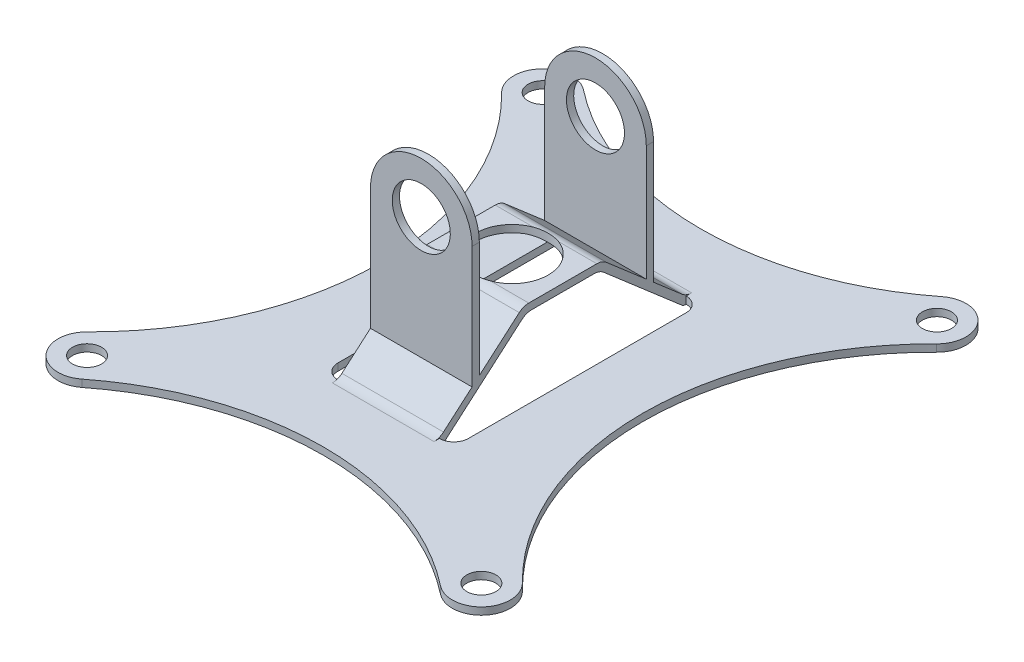
SolidWorks part; units mm, degrees
ref_plane "Front Plane" through (0, 0, 0) normal (0, 0, 1) x (1, 0, 0)
ref_plane "Top Plane" through (0, 0, 0) normal (0, 1, 0) x (1, 0, 0)
ref_plane "Right Plane" through (0, 0, 0) normal (1, 0, 0) x (0, 0, -1)
sketch "Sketch1" plane through (0, 0, 0) normal (0, 1, 0) x (1, 0, 0)
  line L0 (-86.233, 99.6442) -> (86.233, 99.6442) construction
  line L1 (-12.7, 0) -> (12.7, 0) construction
  line L2 (-86.233, -99.6442) -> (86.233, -99.6442) construction
  line L3 (0, -53.975) -> (0, 53.975) construction
  line L4 (-22.225, -53.975) -> (22.225, -53.975)
  line L5 (-28.575, -47.625) -> (-28.575, 47.625)
  line L6 (-22.225, 53.975) -> (22.225, 53.975)
  line L7 (28.575, -47.625) -> (28.575, 47.625)
  line L8 (-28.575, -53.975) -> (28.575, 53.975) construction
  line L9 (-28.575, 53.975) -> (28.575, -53.975) construction
  circle A0 centre (-86.233, 99.6442) radius 6.35
  circle A1 centre (86.233, 99.6442) radius 6.35
  arc A2 (-78.3936, 109.6359) -> (-95.1343, 90.5856) centre (-86.233, 99.6442) ccw
  arc A3 (95.1343, 90.5856) -> (78.3936, 109.6359) centre (86.233, 99.6442) ccw
  arc A4 (-78.3936, 109.6359) -> (78.3936, 109.6359) centre (0, 209.5531) ccw
  arc A5 (-78.3936, -109.6359) -> (78.3936, -109.6359) centre (0, -209.5531) cw
  arc A6 (95.1343, -90.5856) -> (78.3936, -109.6359) centre (86.233, -99.6442) cw
  arc A7 (-78.3936, -109.6359) -> (-95.1343, -90.5856) centre (-86.233, -99.6442) cw
  circle A8 centre (86.233, -99.6442) radius 6.35
  circle A9 centre (-86.233, -99.6442) radius 6.35
  arc A10 (-95.1343, 90.5856) -> (-95.1343, -90.5856) centre (-184.1469, 0) cw
  arc A11 (95.1343, 90.5856) -> (95.1343, -90.5856) centre (184.1469, 0) ccw
  arc A12 (-22.225, 53.975) -> (-28.575, 47.625) centre (-22.225, 47.625) ccw
  arc A13 (22.225, 53.975) -> (28.575, 47.625) centre (22.225, 47.625) cw
  arc A14 (22.225, -53.975) -> (28.575, -47.625) centre (22.225, -47.625) ccw
  arc A15 (-28.575, -47.625) -> (-22.225, -53.975) centre (-22.225, -47.625) ccw
  arc A21 (90.6836, 95.1149) -> (82.3133, 104.6401) centre (86.233, 99.6442) ccw
  arc A23 (-82.3133, 104.6401) -> (-90.6836, 95.1149) centre (-86.233, 99.6442) ccw
  arc A25 (-82.3133, -104.6401) -> (-90.6836, -95.1149) centre (-86.233, -99.6442) cw
  arc A27 (90.6836, -95.1149) -> (82.3133, -104.6401) centre (86.233, -99.6442) cw
  arc A29 (-82.3133, -104.6401) -> (82.3133, -104.6401) centre (0, -209.5531) cw construction
  arc A30 (-82.3133, 104.6401) -> (82.3133, 104.6401) centre (0, 209.5531) ccw construction
  arc A34 (-90.6836, 95.1149) -> (-90.6836, -95.1149) centre (-184.1469, 0) cw construction
  arc A35 (90.6836, 95.1149) -> (90.6836, -95.1149) centre (184.1469, 0) ccw construction
  point P4 (0, 99.6442)
  point P13 (0, 0)
  point P26 (0, 0)
  dimension "D1" = 172.466
  dimension "D3" = 12.7
  dimension "D4" = 127
  dimension "D6" = 127
  dimension "D7" = 25.4
  dimension "D11" = 6.35
  dimension "D2" = 99.6442
  dimension "D5" = 25.4
  dimension "D9" = 57.15
  dimension "D10" = 107.95
  dimension "D14" = 6.35
extrude "Boss-Extrude1" add sketch "Sketch1" along normal blind 3.175
sketch "Sketch4" plane through (0, 0, 0) normal (1, 0, 0) x (0, 0, -1)
  line L0 (-90.5856, 0) -> (90.5856, 0) construction
  line L1 (-53.975, 3.175) -> (-19.05, 33.3781)
  line L2 (-14.8963, 34.925) -> (14.8963, 34.925)
  line L3 (-36.5125, 18.2765) -> (-36.5125, 3.175) construction
  line L4 (90.5856, 3.175) -> (-90.5856, 3.175) construction
  line L5 (-51.8982, 0.7735) -> (-17.8676, 30.2031)
  line L6 (-13.7139, 31.75) -> (13.7139, 31.75)
  line L7 (-53.975, 3.175) -> (-53.975, 0)
  line L8 (0, 34.925) -> (0, 0) construction
  line L9 (36.5125, 18.2765) -> (36.5125, 3.175) construction
  line L10 (53.975, 3.175) -> (53.975, 0)
  line L11 (51.8982, 0.7735) -> (17.8676, 30.2031)
  line L12 (53.975, 3.175) -> (19.05, 33.3781)
  line L13 (-36.5125, 18.2765) -> (-36.5125, 91.0082)
  line L14 (-36.5125, 91.0082) -> (-39.6875, 91.0082)
  line L15 (-39.6875, 91.0082) -> (-39.6875, 15.5308)
  line L16 (39.6875, 91.0082) -> (39.6875, 15.5308)
  line L17 (36.5125, 91.0082) -> (39.6875, 91.0082)
  line L18 (36.5125, 18.2765) -> (36.5125, 91.0082)
  arc A0 (-53.975, 0) -> (-51.8982, 0.7735) centre (-53.975, 3.175) ccw
  arc A1 (-17.8676, 30.2031) -> (-13.7139, 31.75) centre (-13.7139, 25.4) cw
  arc A2 (-19.05, 33.3781) -> (-14.8963, 34.925) centre (-14.8963, 28.575) cw
  arc A3 (19.05, 33.3781) -> (14.8963, 34.925) centre (14.8963, 28.575) ccw
  arc A4 (17.8676, 30.2031) -> (13.7139, 31.75) centre (13.7139, 25.4) ccw
  arc A5 (53.975, 0) -> (51.8982, 0.7735) centre (53.975, 3.175) cw
  point P33 (0, 31.75)
  dimension "D1" = 31.75
  dimension "D5" = 6.35
  dimension "D2" = 3.175
  dimension "D3" = 3.175
  dimension "D4" = 36.5125
  dimension "D6" = 87.8332
extrude "Boss-Extrude3" add sketch "Sketch4" along normal mid plane 44.45 contours A5 L10 L12 A3 L2 A2 L1 L7 A0 L5 A1 L6 A4 L11 | L14 L15 L1 L13 | L18 L12 L16 L17 region at (0, 8.4947, 46.0891) region at (0, 53.9517, 38.1098) region at (0, 53.9517, -38.1098)
sketch "Sketch5" plane through (0, 34.925, 0) normal (0, 1, 0) x (1, 0, 0)
  circle A0 centre (0, 0) radius 15.875
  dimension "D1" = 31.75
extrude "Cut-Extrude1" cut sketch "Sketch5" against normal through all
sketch "Sketch6" plane through (0, 0, -39.6875) normal (0, 0, -1) x (-1, 0, 0)
  line L0 (-22.225, 91.0082) -> (22.225, 91.0082) construction
  line L1 (22.225, 91.0082) -> (22.225, 15.5308) construction
  line L2 (-22.225, 91.0082) -> (-22.225, 15.5308) construction
  line L3 (22.225, 91.0082) -> (22.225, 15.5308)
  line L4 (-22.225, 91.0082) -> (-22.225, 15.5308)
  line L5 (-22.225, 91.0082) -> (22.225, 91.0082)
  circle A0 centre (0, 68.7832) radius 22.225
  circle A1 centre (0, 68.7832) radius 12.7
  line M4 (22.225, 91.0082) -> (-22.225, 91.0082)
  line M5 (-22.225, 91.0082) -> (-22.225, 15.5308)
  dimension "D1" = 44.45
  dimension "D2" = 25.4
extrude "Cut-Extrude2" cut sketch "Sketch6" against normal up to surface (79.375 mm away) contours A1 | A0 L5 M5 | A0 L3 M4 region at (-17.2606, 86.0438, -39.6875) region at (17.2606, 86.0438, -39.6875) region at (0, 68.7832, -39.6875) up to face at (0, 53.2695, 39.6875)
fillet "Fillet1" radius 6.35 2 edges at (0, 3.175, 53.975) (0, 3.175, -53.975)
extrude "holes" cut sketch "Sketch1<5>" along normal through all contours A9 | A8 | A0 | A1 region at (-86.233, 0, -99.6442) region at (86.233, 0, -99.6442) region at (86.233, 0, 99.6442) region at (-86.233, 0, 99.6442)
sketch "Sketch1<5>" plane through (0, 0, 0) normal (0, 1, 0) x (1, 0, 0) same geometry as "Sketch1"
sketch "Sketch7" plane through (0, 3.175, 0) normal (0, 1, 0) x (1, 0, 0)
  line L0 (-86.233, 99.6442) -> (86.233, -99.6442) construction
  line L1 (-86.233, -99.6442) -> (86.233, 99.6442) construction
  line L2 (0, 82.5531) -> (0, -82.5531) construction
  circle A0 centre (-73.7669, 85.2394) radius 6.35
  circle A1 centre (-73.7669, -85.2394) radius 6.35
  circle A2 centre (-86.233, -99.6442) radius 6.35 construction
  arc A3 (-78.3936, 109.6359) -> (78.3936, 109.6359) centre (0, 209.5531) ccw construction
  arc A4 (78.3936, -109.6359) -> (-78.3936, -109.6359) centre (0, -209.5531) ccw construction
  circle A5 centre (73.7669, -85.2394) radius 6.35
  circle A6 centre (73.7669, 85.2394) radius 6.35
  circle A10 centre (-86.233, 99.6442) radius 6.35 construction
  circle A11 centre (86.233, -99.6442) radius 6.35 construction
  dimension "D1" = 19.05
  dimension "D2" = 19.05
extrude "DH" [suppressed] cut sketch "Sketch7" against normal through all
sketch "Sketch8" plane through (0, 3.175, 0) normal (0, 1, 0) x (1, 0, 0)
  line L0 (0, 82.5531) -> (0, -82.5531) construction
  arc A0 (-81.7824, 104.1735) -> (-81.7824, -104.1735) centre (-184.1469, 0) cw
  circle A1 centre (-86.233, -99.6442) radius 6.35 construction
  circle A2 centre (-86.233, 99.6442) radius 6.35 construction
  arc A3 (-95.1343, -90.5856) -> (-95.1343, 90.5856) centre (-184.1469, 0) ccw construction
  arc A4 (-90.6836, 95.1149) -> (-90.6836, -95.1149) centre (-184.1469, 0) cw
  arc A5 (-90.6836, -95.1149) -> (-81.7824, -104.1735) centre (-86.233, -99.6442) ccw
  arc A6 (-81.7824, 104.1735) -> (-90.6836, 95.1149) centre (-86.233, 99.6442) ccw
  arc A7 (-78.3936, 109.6359) -> (78.3936, 109.6359) centre (0, 209.5531) ccw construction
  arc A8 (78.3936, -109.6359) -> (-78.3936, -109.6359) centre (0, -209.5531) ccw construction
  arc A9 (81.7824, 104.1735) -> (90.6836, 95.1149) centre (86.233, 99.6442) cw
  arc A10 (90.6836, -95.1149) -> (81.7824, -104.1735) centre (86.233, -99.6442) cw
  arc A11 (90.6836, 95.1149) -> (90.6836, -95.1149) centre (184.1469, 0) ccw
  arc A12 (81.7824, 104.1735) -> (81.7824, -104.1735) centre (184.1469, 0) ccw
extrude "slots" [suppressed] cut sketch "Sketch8" against normal through all
other "PropertyManager"
